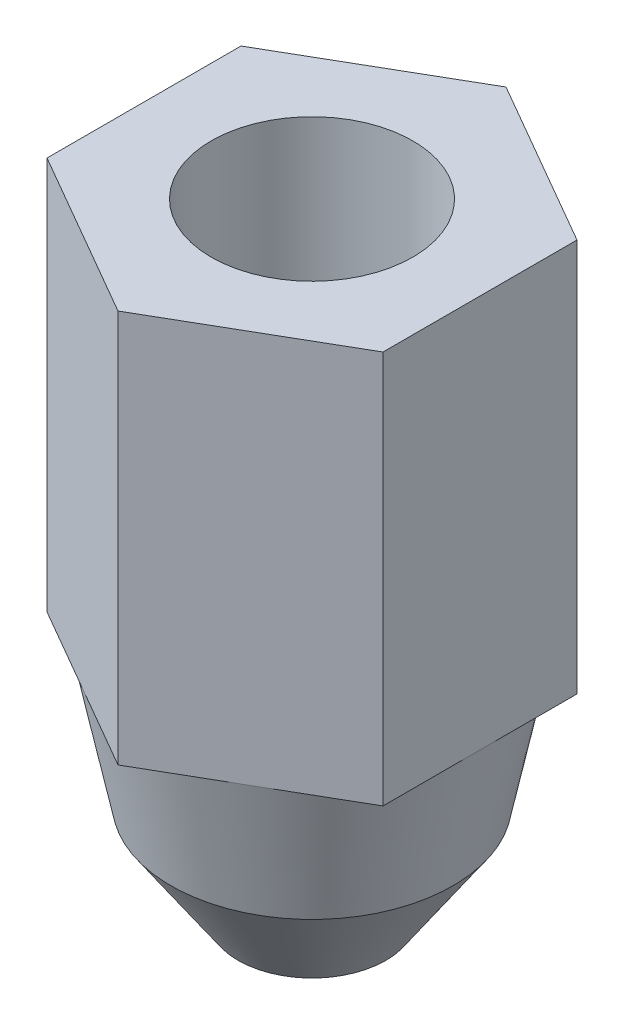
SolidWorks part; units mm, degrees
ref_plane "Front Plane" through (0, 0, 0) normal (0, 0, 1) x (1, 0, 0)
ref_plane "Top Plane" through (0, 0, 0) normal (0, 1, 0) x (1, 0, 0)
ref_plane "Right Plane" through (0, 0, 0) normal (1, 0, 0) x (0, 0, -1)
sketch "Sketch1" plane through (0, 0, 0) normal (0, 1, 0) x (1, 0, 0)
  line L0 (5, -2.8868) -> (0, -5.7735)
  line L1 (0, -5.7735) -> (-5, -2.8868)
  line L2 (-5, -2.8868) -> (-5, 2.8868)
  line L3 (-5, 2.8868) -> (0, 5.7735)
  line L4 (0, 5.7735) -> (5, 2.8868)
  line L5 (5, 2.8868) -> (5, -2.8868)
extrude "Boss-Extrude1" add sketch "Sketch1" against normal blind 11.7
sketch "Sketch2" plane through (0, 0, 0) normal (0, 0, 1) x (1, 0, 0)
  line L0 (0, -11.7) -> (5, -11.7)
  line L1 (5, -11.7) -> (4.2, -15.6)
  line L2 (4.2, -15.6) -> (2.2, -18.525)
  line L3 (2.2, -18.525) -> (0, -19.5)
  line L4 (0, -19.5) -> (0, -11.7)
  line L5 (0, -10) -> (0, 1000) construction
revolve "Revolve1" add sketch "Sketch2" angle 360 about L5
sketch "Sketch3" plane through (0, 0, 0) normal (0, 1, 0) x (1, 0, 0)
  circle A0 centre (0, 0) radius 3
extrude "Cut-Extrude1" cut sketch "Sketch3" against normal blind 12
